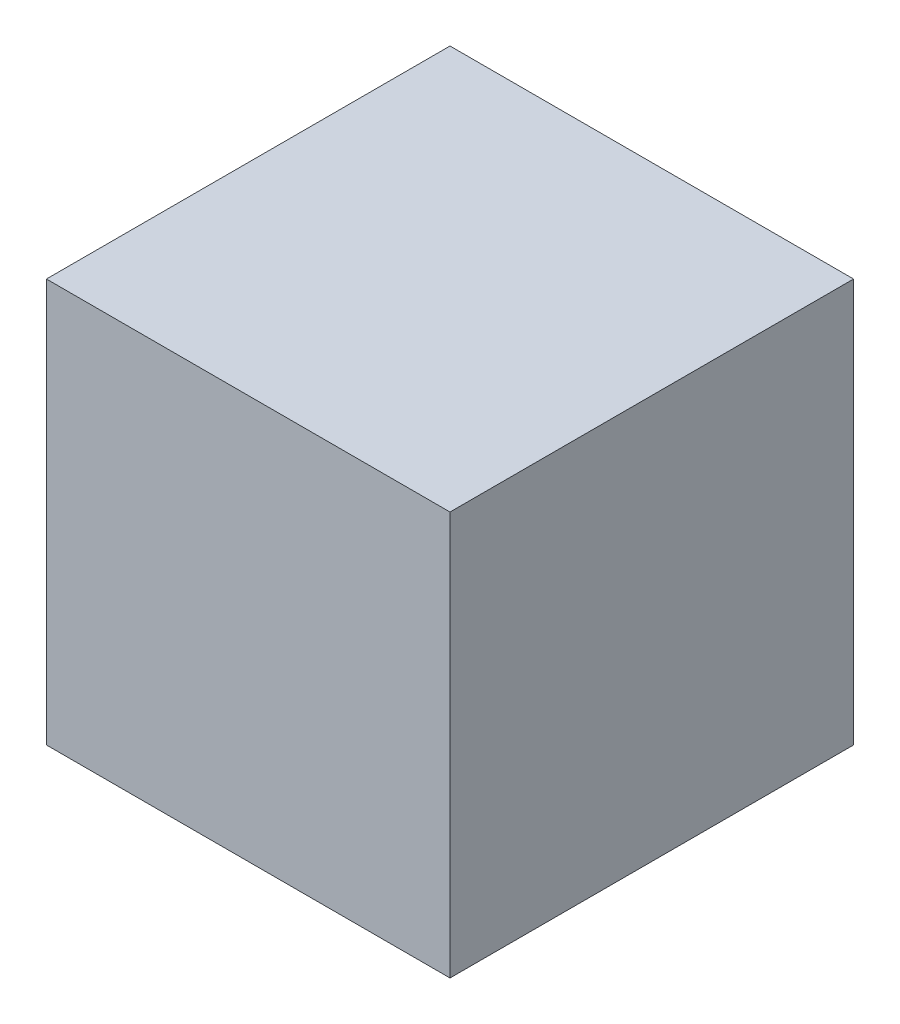
SolidWorks part; units mm, degrees
ref_plane "Front Plane" through (0, 0, 0) normal (0, 0, 1) x (1, 0, 0)
ref_plane "Top Plane" through (0, 0, 0) normal (0, 1, 0) x (1, 0, 0)
ref_plane "Right Plane" through (0, 0, 0) normal (1, 0, 0) x (0, 0, -1)
sketch "Sketch1" plane through (0, 0, 0) normal (0, 1, 0) x (1, 0, 0)
  line L0 (0, 0) -> (50.8, 0)
  line L1 (0, 0) -> (0, 50.8)
  line L2 (50.8, 0) -> (50.8, 50.8)
  line L3 (0, 50.8) -> (50.8, 50.8)
  dimension "D1" = 50.8
  dimension "D2" = 50.8
extrude "Extrude-Thin1" add sketch "Sketch1" along normal blind 50.8 thin thin type one direction reverse wall 6.35
sketch "Sketch2" plane through (0, 50.8, 0) normal (0, 1, 0) x (1, 0, 0)
  line L0 (6.35, 6.35) -> (44.45, 6.35)
  line L1 (6.35, 6.35) -> (6.35, 44.4582)
  line L2 (44.45, 6.35) -> (44.45, 44.4582)
  line L3 (6.35, 44.4582) -> (44.45, 44.4582)
extrude "Boss-Extrude1" add sketch "Sketch2" against normal blind 6.35
sketch "Sketch3" plane through (0, 0, 0) normal (0, -1, 0) x (1, 0, 0)
  line L0 (6.35, -44.45) -> (44.45, -44.45)
  line L1 (6.35, -44.45) -> (6.35, -6.3418)
  line L2 (44.45, -44.45) -> (44.45, -6.3418)
  line L3 (6.35, -6.3418) -> (44.45, -6.3418)
extrude "Boss-Extrude3" add sketch "Sketch3" against normal blind 6.35
